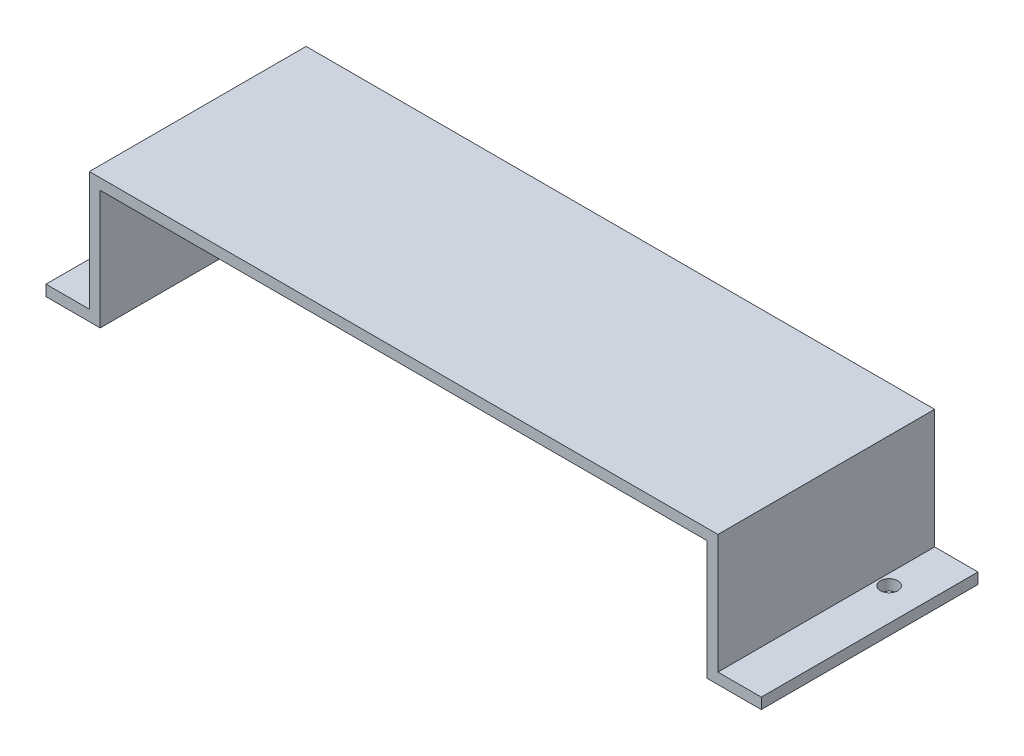
SolidWorks part; units mm, degrees
ref_plane "Front Plane" through (0, 0, 0) normal (0, 0, 1) x (1, 0, 0)
ref_plane "Top Plane" through (0, 0, 0) normal (0, 1, 0) x (1, 0, 0)
ref_plane "Right Plane" through (0, 0, 0) normal (1, 0, 0) x (0, 0, -1)
sketch "Sketch1" plane through (0, 0, 0) normal (0, 1, 0) x (1, 0, 0)
  line L1 (-88.9, 31.75) -> (88.9, 31.75)
  line L2 (-88.9, 31.75) -> (-88.9, -31.75)
  line L3 (-88.9, -31.75) -> (88.9, -31.75)
  line L4 (88.9, 31.75) -> (88.9, -31.75)
  line L5 (-88.9, 31.75) -> (88.9, -31.75) construction
  line L6 (-88.9, -31.75) -> (88.9, 31.75) construction
  point P0 (0, 0)
  dimension "D1" = 177.8
  dimension "D2" = 63.5
extrude "Boss-Extrude1" add sketch "Sketch1" along normal blind 3.175
sketch "Sketch3" plane through (0, 3.175, 0) normal (0, 1, 0) x (1, 0, 0)
  line L0 (-88.9, -31.75) -> (88.9, -31.75) construction
  line L1 (-88.9, 31.75) -> (-92.075, 31.75)
  line L2 (-88.9, 31.75) -> (-88.9, -31.75)
  line L3 (-88.9, -31.75) -> (-92.075, -31.75)
  line L4 (-92.075, 31.75) -> (-92.075, -31.75)
  line L5 (0, -55) -> (0, 55) construction
  line L6 (88.9, -31.75) -> (92.075, -31.75)
  line L7 (92.075, 31.75) -> (92.075, -31.75)
  line L8 (88.9, 31.75) -> (92.075, 31.75)
  line L9 (88.9, 31.75) -> (88.9, -31.75)
  dimension "D1" = 3.175
extrude "Boss-Extrude2" add sketch "Sketch3" against normal blind 38.1
sketch "Sketch4" plane through (92.075, 0, 0) normal (1, 0, 0) x (0, 0, -1)
  line L0 (31.75, -34.925) -> (31.75, 3.175) construction
  line L1 (-31.75, -34.925) -> (31.75, -34.925)
  line L2 (-31.75, -34.925) -> (-31.75, -31.75)
  line L3 (-31.75, -31.75) -> (31.75, -31.75)
  line L4 (31.75, -34.925) -> (31.75, -31.75)
  dimension "D1" = 3.175
extrude "Boss-Extrude3" add sketch "Sketch4" along normal blind 12.7
sketch "Sketch5" plane through (0, -34.925, 0) normal (0, -1, 0) x (1, 0, 0)
  line L0 (88.9, -31.75) -> (88.9, 31.75) construction
  line L1 (104.775, -31.75) -> (88.9, -31.75) construction
  circle A0 centre (95.25, -15.24) radius 2.54
  dimension "D1" = 5.08
  dimension "D2" = 6.35
  dimension "D3" = 16.51
extrude "Cut-Extrude1" cut sketch "Sketch5" against normal blind 12.7
mirror "Mirror1" about plane through (0, 0, 0) normal (1, 0, 0) of "Boss-Extrude3", "Cut-Extrude1"
